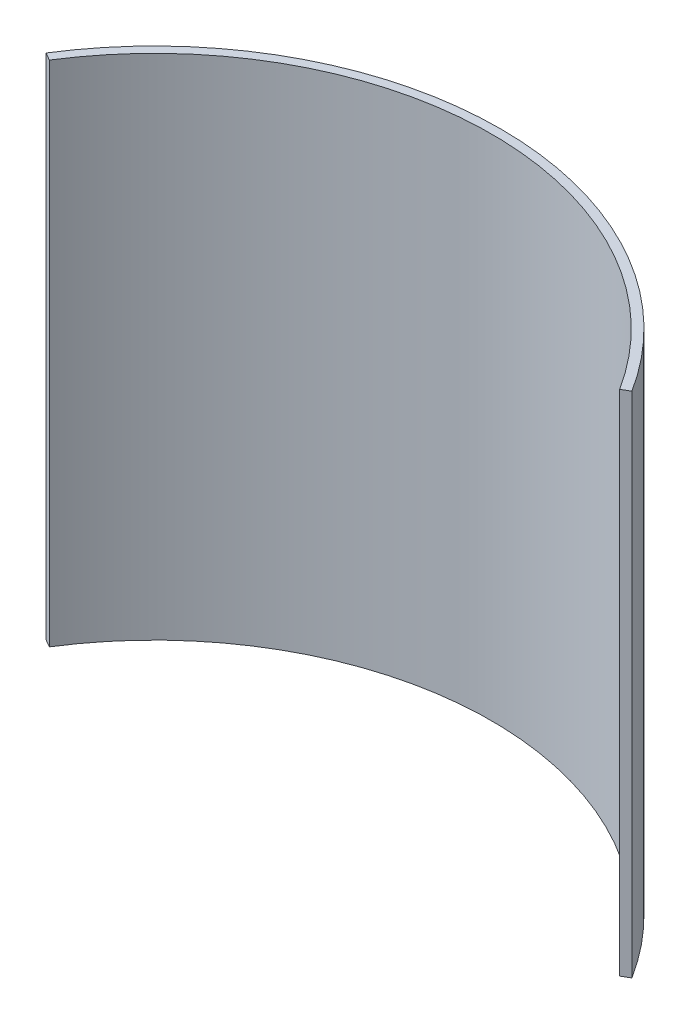
SolidWorks part; units mm, degrees
ref_plane "Front Plane" through (0, 0, 0) normal (0, 0, 1) x (1, 0, 0)
ref_plane "Top Plane" through (0, 0, 0) normal (0, 1, 0) x (1, 0, 0)
ref_plane "Right Plane" through (0, 0, 0) normal (1, 0, 0) x (0, 0, -1)
sketch "Sketch1" plane through (0, 0, 0) normal (0, 1, 0) x (1, 0, 0)
  line L0 (0, 45.7344) -> (0, 0) construction
  line L3 (-31.7, 20.034) -> (-32.5667, 20.5344)
  line L4 (39.6072, -22.8672) -> (0, 0) construction
  line L7 (-39.6072, -22.8672) -> (0, 0) construction
  line L8 (31.7, 20.034) -> (32.5667, 20.5344)
  arc A2 (32.5667, 20.5344) -> (-32.5667, 20.5344) centre (0, 0) ccw
  arc A3 (31.7, 20.034) -> (-31.7, 20.034) centre (0, 0) ccw
  dimension "D4" = 3
extrude "Boss-Extrude1" add sketch "Sketch1" against normal blind 56.5
